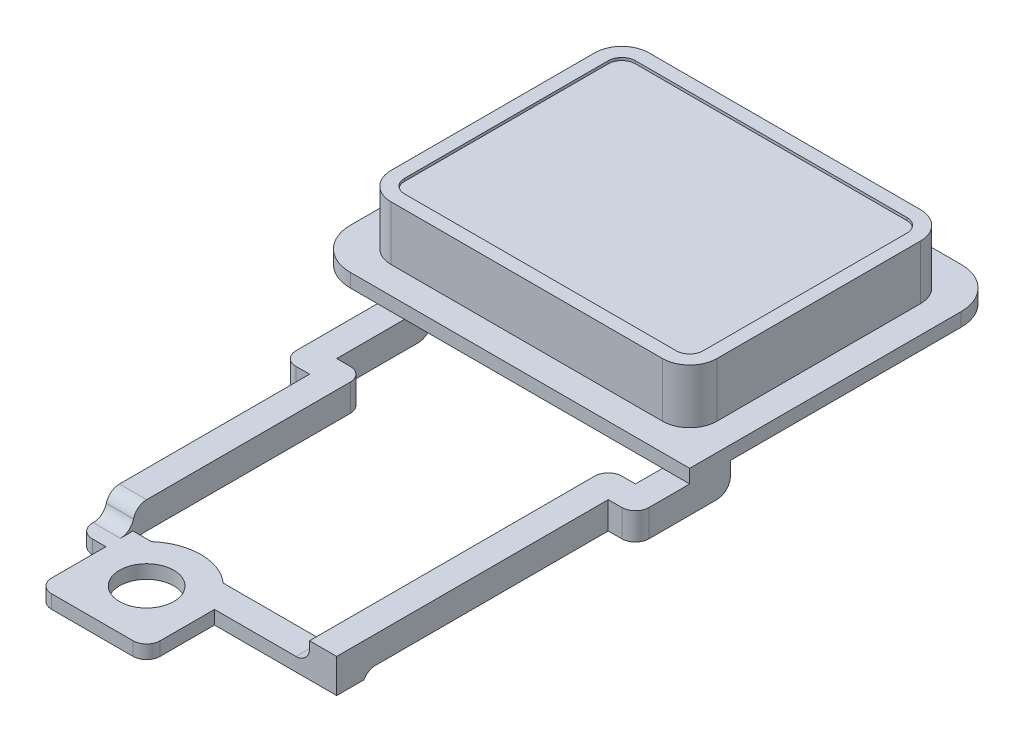
SolidWorks part; units mm, degrees
material "ABS"
ref_plane "Front Plane" through (0, 0, 0) normal (0, 0, 1) x (1, 0, 0)
ref_plane "Top Plane" through (0, 0, 0) normal (0, 1, 0) x (1, 0, 0)
ref_plane "Right Plane" through (0, 0, 0) normal (1, 0, 0) x (0, 0, -1)
sketch "Sketch1" plane through (0, 0, 0) normal (0, 1, 0) x (1, 0, 0)
  line L1 (0, 0) -> (12, 0)
  line L2 (0, 0) -> (0, 9.5)
  line L3 (0, 9.5) -> (12, 9.5)
  line L4 (12, 0) -> (12, 9.5)
  dimension "D1" = 12
  dimension "D2" = 9.5
extrude "Boss-Extrude1" add sketch "Sketch1" along normal blind 2
sketch "Sketch2" plane through (0, 2, 0) normal (0, 1, 0) x (1, 0, 0)
  line L0 (12, 0) -> (12, 9.5) construction
  line L1 (0.5, 9) -> (11.5, 9)
  line L2 (0.5, 9) -> (0.5, 0.5)
  line L3 (0.5, 0.5) -> (11.5, 0.5)
  line L4 (11.5, 9) -> (11.5, 0.5)
  line L5 (12, 9.5) -> (0, 9.5) construction
  line L6 (0, 9.5) -> (0, 0) construction
  line L7 (0, 0) -> (12, 0) construction
  dimension "D1" = 0.5
  dimension "D2" = 0.5
  dimension "D3" = 0.5
  dimension "D4" = 0.5
extrude "Cut-Extrude1" cut sketch "Sketch2" against normal blind 0.1
fillet "Fillet1" radius 0.5 4 edges at (11.5, 1.95, -0.5) (0.5, 1.95, -0.5) (0.5, 1.95, -9) (11.5, 1.95, -9)
fillet "Fillet2" radius 1 4 edges at (12, 1, -9.5) (0, 1, -9.5) (0, 1, 0) (12, 1, 0)
sketch "Sketch3" plane through (0, 0, 0) normal (0, -1, 0) x (1, 0, 0)
  line L1 (-1, 1) -> (13, 1)
  line L2 (-1, 1) -> (-1, -10.5)
  line L3 (-1, -10.5) -> (13, -10.5)
  line L4 (13, 1) -> (13, -10.5)
  line L5 (1, 0) -> (11, 0) construction
  line L6 (0, -8.5) -> (0, -1) construction
  line L7 (12, -1) -> (12, -8.5) construction
  line L8 (11, -9.5) -> (1, -9.5) construction
  dimension "D1" = 1
  dimension "D2" = 1
  dimension "D3" = 1
  dimension "D4" = 1
extrude "Boss-Extrude2" add sketch "Sketch3" along normal blind 0.5
sketch "Sketch6" plane through (0, -0.5, 0) normal (0, -1, 0) x (1, 0, 0)
  line L0 (13, -10.5) -> (13, 1) construction
  line L1 (13, -0.5) -> (12, -0.5)
  line L2 (13, -0.5) -> (13, 3)
  line L3 (13, 3) -> (12, 3)
  line L4 (12, -0.5) -> (12, 2)
  line L5 (13, 1) -> (-1, 1) construction
  line L7 (12, 2) -> (11, 2)
  line L8 (12, 3) -> (12, 13)
  line L9 (12, 13) -> (11, 13)
  line L10 (11, 2) -> (11, 13)
  line L11 (3.5, 12) -> (2.5, 12)
  line L12 (3.5, 12) -> (3.5, 3.5)
  line L13 (3.5, 3.5) -> (2.5, 3.5)
  line L14 (2.5, 12) -> (2.5, 4.5)
  line L15 (2.5, 4.5) -> (1.5, 4.5)
  line L16 (2.5, 3.5) -> (2.5, 0)
  line L17 (2.5, 0) -> (1.5, 0)
  line L18 (1.5, 4.5) -> (1.5, 0)
  dimension "D1" = 1.5
  dimension "D2" = 1
  dimension "D3" = 3.5
  dimension "D4" = 1
  dimension "D5" = 1
  dimension "D6" = 11
  dimension "D7" = 1
  dimension "D8" = 7.5
  dimension "D9" = 7.5
  dimension "D10" = 1
  dimension "D11" = 1
  dimension "D12" = 4.5
  dimension "D13" = 1
extrude "Boss-Extrude5" add sketch "Sketch6" along normal blind 1
sketch "Sketch7" plane through (0, -1.5, 0) normal (0, -1, 0) x (1, 0, 0)
  line L1 (2.5, 13) -> (12, 13)
  line L2 (2.5, 13) -> (2.5, 12)
  line L3 (2.5, 12) -> (12, 12)
  line L4 (12, 13) -> (12, 12)
  dimension "D1" = 1
extrude "Boss-Extrude6" add sketch "Sketch7" along normal blind 0.25 and the other way blind 0.25
sketch "Sketch9" plane through (0, -1.25, 0) normal (0, 1, 0) x (1, 0, 0)
  line L0 (6.8229, -12) -> (7.5, -12)
  line L1 (3.5, -12) -> (4.1771, -12)
  line L2 (3.5, -12) -> (3.5, -15.5)
  line L3 (3.5, -15.5) -> (7.5, -15.5)
  line L4 (7.5, -12) -> (7.5, -15.5)
  arc A0 (6.8229, -12) -> (4.1771, -12) centre (5.5, -13.5) ccw
  dimension "D3" = 4
  dimension "D4" = 2
  dimension "D5" = 2
  dimension "D1" = 4
  dimension "D2" = 3.5
extrude "Boss-Extrude7" add sketch "Sketch9" against normal blind 0.5
sketch "Sketch10" plane through (0, -1.25, 0) normal (0, 1, 0) x (1, 0, 0)
  line L0 (3.5, -13) -> (3.5, -15.5) construction
  line L1 (3.5, -15.5) -> (7.5, -15.5) construction
  circle A0 centre (5.5, -13.5) radius 1
  dimension "D1" = 2
  dimension "D2" = 2
  dimension "D3" = 2
extrude "Cut-Extrude2" cut sketch "Sketch10" against normal up to next
fillet "Fillet4" radius 0.5 12 edges at (11, -1.25, 12.5) (2.5, -1.5, 13) (3.5, -1, 3.5) (1.5, -1, 4.5) (13, -1, 3) (11, -1, 2) (12.5, -1.5, -0.5) (2, -1.5, 0) (3, -1.5, 12) (3, -0.5, 12) (7.5, -1.5, 15.5) (3.5, -1.5, 15.5)
fillet "Fillet5" radius 0.5 2 edges at (3, -1.25, 12) (11.5, -1.5, 12)
fillet "Fillet6" radius 1.5 3 edges at (13, -0.25, -10.5) (-1, -0.25, 1) (-1, -0.25, -10.5)
sketch "Sketch11" plane through (0, -0.5, 0) normal (0, -1, 0) x (1, 0, 0)
  line L0 (0.5, -10.5) -> (11.5, -10.5) construction
  line L1 (0.5, -1) -> (11, -1)
  line L2 (0.5, -1) -> (0.5, -8.5)
  line L3 (0.5, -8.5) -> (11, -8.5)
  line L4 (11, -1) -> (11, -8.5)
  line L5 (-1, -0.5) -> (-1, -9) construction
  line L6 (13, -9) -> (13, -0.5) construction
  line L7 (12, 1) -> (2.5, 1) construction
  dimension "D1" = 2
  dimension "D2" = 1.5
  dimension "D3" = 2
  dimension "D4" = 2
extrude "Cut-Extrude3" cut sketch "Sketch11" against normal blind 0.3
fillet "Fillet7" radius 0.3 4 edges at (11, -0.35, -1) (0.5, -0.35, -8.5) (0.5, -0.35, -1) (11, -0.35, -8.5)
